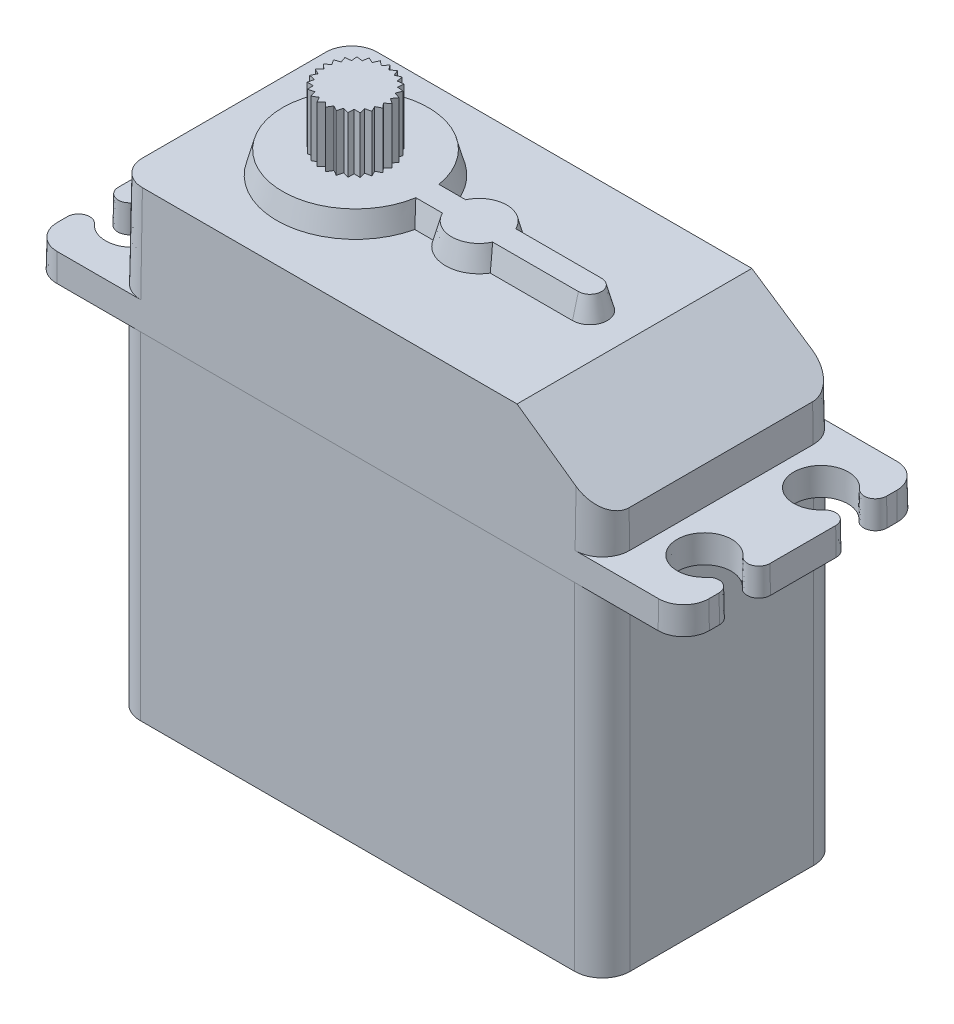
SolidWorks part; units mm, degrees
ref_plane "Front Plane" through (0, 0, 0) normal (0, 0, 1) x (1, 0, 0)
ref_plane "Top Plane" through (0, 0, 0) normal (0, 1, 0) x (1, 0, 0)
ref_plane "Right Plane" through (0, 0, 0) normal (1, 0, 0) x (0, 0, -1)
sketch "Sketch1" plane through (0, 0, 0) normal (0, 1, 0) x (1, 0, 0)
  line L1 (-18.6187, -10.25) -> (18.6187, -10.25)
  line L2 (-21, -7.8687) -> (-21, 7.8687)
  line L3 (-18.6187, 10.25) -> (18.6187, 10.25)
  line L4 (21, -7.8687) -> (21, 7.8687)
  line L5 (-21, -10.25) -> (21, 10.25) construction
  line L6 (-21, 10.25) -> (21, -10.25) construction
  arc A0 (-18.6187, -10.25) -> (-21, -7.8687) centre (-18.6187, -7.8688) cw
  arc A1 (18.6187, -10.25) -> (21, -7.8687) centre (18.6188, -7.8688) ccw
  arc A2 (18.6187, 10.25) -> (21, 7.8687) centre (18.6188, 7.8688) cw
  arc A3 (-21, 7.8687) -> (-18.6187, 10.25) centre (-18.6187, 7.8688) cw
  point P0 (0, 0)
  dimension "D3" = 2.3813
  dimension "D1" = 20.5
  dimension "D2" = 42
extrude "Boss-Extrude1" add sketch "Sketch1" against normal blind 28.88
extrude "Boss-Extrude2" add sketch "Sketch1<2>" along normal blind 10.6 draft 1
sketch "Sketch1<2>" plane through (0, 0, 0) normal (0, 1, 0) x (1, 0, 0) same geometry as "Sketch1"
sketch "Sketch2" plane through (0, 0, 0) normal (0, 1, 0) x (1, 0, 0)
  line L1 (-25.7788, 10.25) -> (25.7788, 10.25)
  line L2 (-27.975, 8.0538) -> (-27.975, 7.1827)
  line L3 (-25.7788, -10.25) -> (25.7788, -10.25)
  line L4 (27.975, 8.0538) -> (27.975, 7.1827)
  line L7 (-18.6187, -10.25) -> (18.6187, -10.25) construction
  line L8 (18.6187, 10.25) -> (-18.6187, 10.25) construction
  line L9 (24.5, 0) -> (-24.5, 0) construction
  line L10 (-26.975, 2.8173) -> (-26.975, 7.1827) construction
  line L11 (0, -5) -> (0, 5) construction
  line L12 (-27.975, 2.8173) -> (-27.975, -2.8173)
  line L13 (-26.975, -7.1827) -> (-26.975, -2.8173) construction
  line L14 (26.975, -7.1827) -> (26.975, -2.8173) construction
  line L16 (26.975, 2.8173) -> (26.975, 7.1827) construction
  line L21 (27.975, -7.1827) -> (27.975, -8.0538)
  line L23 (27.975, 2.8173) -> (27.975, -2.8173)
  line L24 (-27.975, -7.1827) -> (-27.975, -8.0538)
  arc A0 (25.7788, 10.25) -> (27.975, 8.0538) centre (25.7788, 8.0538) cw
  arc A1 (-25.7788, 10.25) -> (-27.975, 8.0538) centre (-25.7788, 8.0538) ccw
  arc A2 (20.815, 7.8687) -> (18.6187, 10.065) centre (18.6188, 7.8688) ccw construction
  arc A3 (-27.975, -8.0538) -> (-25.7788, -10.25) centre (-25.7788, -8.0538) ccw
  arc A4 (25.7788, -10.25) -> (27.975, -8.0538) centre (25.7788, -8.0538) ccw
  arc A5 (-26.225, 3.4787) -> (-26.225, 6.5213) centre (-24.5, 5) ccw
  arc A6 (26.225, 6.5213) -> (26.225, 3.4787) centre (24.5, 5) ccw
  arc A7 (26.225, -3.4787) -> (26.225, -6.5213) centre (24.5, -5) ccw
  arc A8 (-26.225, -6.5213) -> (-26.225, -3.4787) centre (-24.5, -5) ccw
  arc A9 (-26.225, -3.4787) -> (-27.975, -2.8173) centre (-26.975, -2.8173) cw
  arc A10 (-26.225, -6.5213) -> (-27.975, -7.1827) centre (-26.975, -7.1827) ccw
  arc A11 (-26.225, 3.4787) -> (-27.975, 2.8173) centre (-26.975, 2.8173) ccw
  arc A12 (-27.975, 7.1827) -> (-26.225, 6.5213) centre (-26.975, 7.1827) ccw
  arc A13 (26.225, -3.4787) -> (27.975, -2.8173) centre (26.975, -2.8173) ccw
  arc A14 (26.225, -6.5213) -> (27.975, -7.1827) centre (26.975, -7.1827) cw
  arc A15 (27.975, 2.8173) -> (26.225, 3.4787) centre (26.975, 2.8173) ccw
  arc A16 (26.225, 6.5213) -> (27.975, 7.1827) centre (26.975, 7.1827) ccw
  point P6 (0, -10.25)
  point P18 (-27.975, -10.25)
  point P21 (27.975, -10.25)
  point P55 (-26.975, 5)
  point P56 (26.975, 5)
  point P57 (26.975, -5)
  point P58 (27.975, 0)
  dimension "D2" = 49
  dimension "D4" = 4.6
  dimension "D5" = 1
  dimension "D1" = 55.95
  dimension "D3" = 10
extrude "Boss-Extrude3" add sketch "Sketch2" along normal blind 2.35 draft 1
sketch "Sketch3" plane through (0, 0, 0) normal (0, 0, 1) x (1, 0, 0)
  line L0 (20.959, 2.35) -> (20.904, 5.5) construction
  line L1 (20.815, 10.6) -> (20.959, 2.35) construction
  line L2 (20.904, 5.5) -> (13.5, 10.6)
  line L3 (-18.6187, 10.6) -> (18.6187, 10.6) construction
  line L4 (13.5, 10.6) -> (20.815, 10.6)
  line L5 (20.815, 10.6) -> (20.904, 5.5)
  line L6 (18.6187, 0) -> (25.7788, 0) construction
  line L7 (21, -28.88) -> (21, 0) construction
  dimension "D1" = 5.5
  dimension "D2" = 7.5
extrude "Cut-Extrude1" cut sketch "Sketch3" against normal through all both and the other way through all
sketch "Sketch4" plane through (0, 10.6, 0) normal (0, 1, 0) x (1, 0, 0)
  line L0 (-7.7932, 0) -> (9.685, 0) construction
  line L1 (-7.7932, 0) -> (-3.1008, 0) construction
  line L2 (-17.165, 6.3699) -> (-17.165, -6.3699) construction
  line L3 (-3.8338, -1.5) -> (-2.2677, -1.5)
  line L4 (2.6377, -1.5) -> (9.685, -1.5)
  line L5 (-3.8338, 1.5) -> (-2.2677, 1.5)
  line L6 (2.6377, 1.5) -> (9.685, 1.5)
  line L7 (-20.815, 7.8687) -> (-20.815, -7.8687) construction
  line L8 (-7.7932, 1.5) -> (-3.1008, 1.5) construction
  line L9 (-7.7932, -1.5) -> (-3.1008, -1.5) construction
  line L10 (11.185, -6.3699) -> (11.185, 6.3699) construction
  arc A0 (-3.8338, 1.5) -> (-3.8338, -1.5) centre (-10.415, 0) ccw
  arc A1 (-2.2677, -1.5) -> (2.6377, -1.5) centre (0.185, 0) ccw
  arc A2 (9.685, 1.5) -> (9.685, -1.5) centre (9.685, 0) cw
  arc A3 (2.6377, 1.5) -> (-2.2677, 1.5) centre (0.185, 0) ccw
  point P1 (11.185, 0)
  point P12 (-17.165, 0)
  dimension "D3" = 6.75
  dimension "D6" = 32
  dimension "D7" = 2.875
  dimension "D4" = 3.65
  dimension "D5" = 21
  dimension "D1" = 1.5
  dimension "D2" = 1.5
extrude "Boss-Extrude4" add sketch "Sketch4" along normal blind 1.9 draft 15
sketch "Sketch5" plane through (0, 12.5, 0) normal (0, 1, 0) x (1, 0, 0)
  circle A0 centre (-10.415, 0) radius 2.95
  dimension "D1" = 5.9
extrude "Boss-Extrude5" add sketch "Sketch5" along normal blind 4.8
ref_axis "Axis1" through (-10.415, 19.2625, 0) along (0, -1, 0)
sketch "Sketch6" plane through (0, 12.5, 0) normal (0, 1, 0) x (1, 0, 0)
  line L0 (-10.415, 0) -> (-10.415, 2.95) construction
  line L1 (-10.415, 0) -> (-9.6813, 2.8573) construction
  line L2 (-10.415, 0) -> (-8.9938, 2.5851) construction
  line L3 (-10.415, 0) -> (-8.3956, 2.1505) construction
  line L4 (-10.415, 0) -> (-7.9242, 1.5807) construction
  line L5 (-10.415, 0) -> (-7.6094, 0.9116) construction
  line L6 (-10.415, 0) -> (-7.4708, 0.1852) construction
  line L7 (-10.415, 0) -> (-7.5172, -0.5528) construction
  line L8 (-10.415, 0) -> (-7.7457, -1.256) construction
  line L9 (-10.415, 0) -> (-8.142, -1.8804) construction
  line L10 (-10.415, 0) -> (-8.681, -2.3866) construction
  line L11 (-10.415, 0) -> (-9.329, -2.7428) construction
  line L12 (-10.415, 0) -> (-10.0452, -2.9267) construction
  line L13 (-10.415, 0) -> (-10.7847, -2.9267) construction
  line L14 (-10.415, 0) -> (-11.5009, -2.7428) construction
  line L15 (-10.415, 0) -> (-12.1489, -2.3866) construction
  line L16 (-10.415, 0) -> (-12.688, -1.8804) construction
  line L17 (-10.415, 0) -> (-13.0842, -1.256) construction
  line L18 (-10.415, 0) -> (-13.3127, -0.5528) construction
  line L19 (-10.415, 0) -> (-13.3592, 0.1852) construction
  line L20 (-10.415, 0) -> (-13.2206, 0.9116) construction
  line L21 (-10.415, 0) -> (-12.9057, 1.5807) construction
  line L22 (-10.415, 0) -> (-12.4344, 2.1505) construction
  line L23 (-10.415, 0) -> (-11.8361, 2.5851) construction
  line L24 (-10.415, 0) -> (-11.1486, 2.8573) construction
  line L25 (-9.1831, -2.2407) -> (-8.681, -2.3866)
  line L26 (-9.329, -2.7428) -> (-9.1831, -2.2407)
  line L27 (-8.681, -2.3866) -> (-8.6646, -1.864)
  line L28 (-8.6646, -1.864) -> (-8.142, -1.8804)
  line L29 (-9.7791, -2.4767) -> (-9.329, -2.7428)
  line L30 (-10.0452, -2.9267) -> (-9.7791, -2.4767)
  line L31 (-10.415, -2.557) -> (-10.0452, -2.9267)
  line L32 (-10.7847, -2.9267) -> (-10.415, -2.557)
  line L33 (-11.0509, -2.4767) -> (-10.7847, -2.9267)
  line L34 (-11.5009, -2.7428) -> (-11.0509, -2.4767)
  line L35 (-11.6468, -2.2407) -> (-11.5009, -2.7428)
  line L36 (-12.1489, -2.3866) -> (-11.6468, -2.2407)
  line L37 (-12.1654, -1.864) -> (-12.1489, -2.3866)
  line L38 (-12.688, -1.8804) -> (-12.1654, -1.864)
  line L39 (-12.5739, -1.3701) -> (-12.688, -1.8804)
  line L40 (-13.0842, -1.256) -> (-12.5739, -1.3701)
  line L41 (-12.8468, -0.7902) -> (-13.0842, -1.256)
  line L42 (-13.3127, -0.5528) -> (-12.8468, -0.7902)
  line L43 (-12.9669, -0.1606) -> (-13.3127, -0.5528)
  line L44 (-13.3592, 0.1852) -> (-12.9669, -0.1606)
  line L45 (-12.9267, 0.4791) -> (-13.3592, 0.1852)
  line L46 (-13.2206, 0.9116) -> (-12.9267, 0.4791)
  line L47 (-12.7286, 1.0887) -> (-13.2206, 0.9116)
  line L48 (-12.9057, 1.5807) -> (-12.7286, 1.0887)
  line L49 (-12.3852, 1.6299) -> (-12.9057, 1.5807)
  line L50 (-12.4344, 2.1505) -> (-12.3852, 1.6299)
  line L51 (-11.9179, 2.0687) -> (-12.4344, 2.1505)
  line L52 (-11.8361, 2.5851) -> (-11.9179, 2.0687)
  line L53 (-11.3563, 2.3774) -> (-11.8361, 2.5851)
  line L54 (-11.1486, 2.8573) -> (-11.3563, 2.3774)
  line L55 (-10.7355, 2.5368) -> (-11.1486, 2.8573)
  line L56 (-10.415, 2.95) -> (-10.7355, 2.5368)
  line L57 (-10.0945, 2.5368) -> (-10.415, 2.95)
  line L58 (-9.6813, 2.8573) -> (-10.0945, 2.5368)
  line L59 (-9.4737, 2.3774) -> (-9.6813, 2.8573)
  line L60 (-8.9938, 2.5851) -> (-9.4737, 2.3774)
  line L61 (-8.912, 2.0687) -> (-8.9938, 2.5851)
  line L62 (-8.3956, 2.1505) -> (-8.912, 2.0687)
  line L63 (-8.4448, 1.6299) -> (-8.3956, 2.1505)
  line L64 (-7.9242, 1.5807) -> (-8.4448, 1.6299)
  line L65 (-8.1013, 1.0887) -> (-7.9242, 1.5807)
  line L66 (-7.6094, 0.9116) -> (-8.1013, 1.0887)
  line L67 (-7.9033, 0.4791) -> (-7.6094, 0.9116)
  line L68 (-7.4708, 0.1852) -> (-7.9033, 0.4791)
  line L69 (-7.863, -0.1606) -> (-7.4708, 0.1852)
  line L70 (-7.5172, -0.5528) -> (-7.863, -0.1606)
  line L71 (-7.9831, -0.7902) -> (-7.5172, -0.5528)
  line L72 (-7.7457, -1.256) -> (-7.9831, -0.7902)
  line L73 (-8.256, -1.3701) -> (-7.7457, -1.256)
  line L74 (-8.142, -1.8804) -> (-8.256, -1.3701)
  circle A1 centre (-10.415, 0) radius 2.95 construction
  point P32 (-10.415, 0)
  point P106 (-10.415, 0)
  dimension "D1" = 25
  dimension "D2" = 25
extrude "Cut-Extrude2" cut sketch "Sketch6" along normal blind 4.8 flip side to cut
